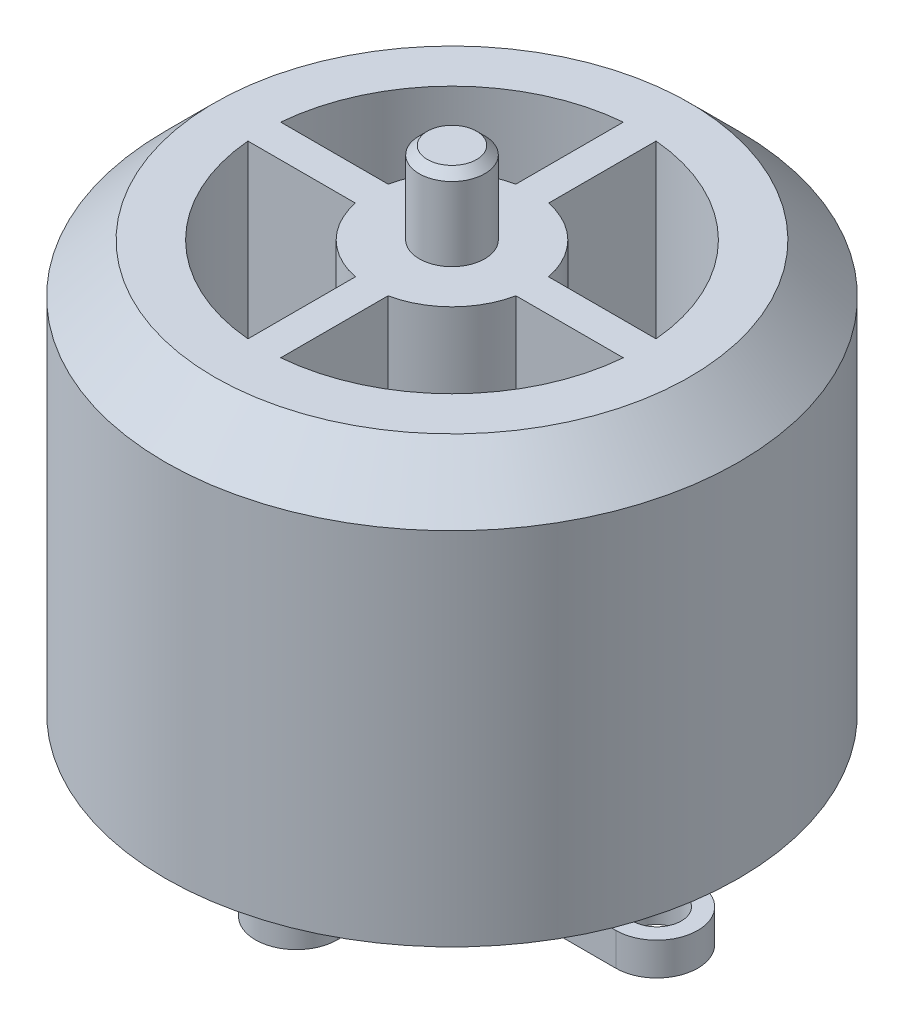
SolidWorks part; units mm, degrees
ref_plane "정면" through (0, 0, 0) normal (0, 0, 1) x (1, 0, 0)
ref_plane "윗면" through (0, 0, 0) normal (0, 1, 0) x (1, 0, 0)
ref_plane "우측면" through (0, 0, 0) normal (1, 0, 0) x (0, 0, -1)
sketch "스케치1" plane through (0, 0, 0) normal (0, 1, 0) x (1, 0, 0)
  line L0 (0, -9.5) -> (0, 9.5) construction
  line L1 (-12.5, 0) -> (12.5, 0) construction
  line L2 (0, -9.5) -> (0, 9.5) construction
  line L3 (-2.5, -9.5) -> (-2.5, 9.5)
  line L4 (2.5, -9.5) -> (2.5, 9.5)
  line L5 (-12.5, 0) -> (12.5, 0) construction
  line L6 (-12.5, 2.5) -> (12.5, 2.5)
  line L7 (-12.5, -2.5) -> (12.5, -2.5)
  circle A0 centre (0, 9.5) radius 1.5
  circle A1 centre (0, -9.5) radius 1.5
  circle A2 centre (-8, 0) radius 1.5
  circle A3 centre (8, 0) radius 1.5
  circle A4 centre (-12.5, 0) radius 1.5
  circle A5 centre (12.5, 0) radius 1.5
  arc A6 (-2.5, -9.5) -> (2.5, -9.5) centre (0, -9.5) ccw
  arc A7 (2.5, 9.5) -> (-2.5, 9.5) centre (0, 9.5) ccw
  arc A8 (-12.5, 2.5) -> (-12.5, -2.5) centre (-12.5, 0) ccw
  arc A9 (12.5, -2.5) -> (12.5, 2.5) centre (12.5, 0) ccw
  circle A10 centre (0, 0) radius 2
  point P4 (0, 0)
  point P8 (0, 0)
  point P17 (0, 0)
  point P23 (0, 0)
  dimension "D1" = 3
  dimension "D5" = 1
  dimension "D6" = 4
  dimension "D2" = 19
  dimension "D3" = 25
  dimension "D4" = 16
extrude "보스-돌출1" add sketch "스케치1" against normal blind 2 contours L6 A8 L7 L3 A4 A2 | A10 | L3 L7 L4 L6 A10 | L3 A6 L4 L7 A1 | L4 A7 L3 L6 A0 | L7 A9 L6 L4 A5 A3 region at (0, 0, 6.5308) region at (-7.5, 0, 2.3654) region at (-2.4293, 0, 0) region at (0, 0, -6.5308) region at (2.6346, 0, 0) region at (0, 0, 0)
extrude "보스-돌출2" add sketch "스케치1<3>" along normal blind 34 contours A10 region at (0, 0, 0)
sketch "스케치1<3>" plane through (0, 0, 0) normal (0, 1, 0) x (1, 0, 0) same geometry as "스케치1"
sketch "스케치2" plane through (0, 0, 0) normal (0, 1, 0) x (1, 0, 0)
  circle A0 centre (0, 0) radius 17.5
  dimension "D1" = 35
extrude "보스-돌출3" add sketch "스케치2" along normal blind 25 from offset 4
chamfer "모따기1" distance 3 angle 45 1 edges at (0, 29, 17.5)
sketch "스케치4" plane through (0, 29, 0) normal (0, 1, 0) x (1, 0, 0)
  line L0 (0, 12.5) -> (0, 4)
  line L1 (-4, 0) -> (-12.5, 0)
  line L2 (-1, 11.4564) -> (-1, 4.899)
  line L3 (-4.899, 1) -> (-11.4564, 1)
  line L4 (11.4564, 1) -> (4.899, 1)
  line L5 (1, 4.899) -> (1, 11.4564)
  line L6 (0, 4) -> (0, 12.5)
  line L7 (12.5, 0) -> (4, 0)
  line L8 (1, -11.4564) -> (1, -4.899)
  line L9 (4.899, -1) -> (11.4564, -1)
  line L10 (4, 0) -> (12.5, 0)
  line L11 (0, -12.5) -> (0, -4)
  line L12 (-11.4564, -1) -> (-4.899, -1)
  line L13 (-1, -4.899) -> (-1, -11.4564)
  line L14 (0, -4) -> (0, -12.5)
  line L15 (-12.5, 0) -> (-4, 0)
  arc A0 (0, 4) -> (-4, 0) centre (0, 0) ccw
  arc A1 (0, 12.5) -> (-12.5, 0) centre (0, 0) ccw
  circle A2 centre (0, 0) radius 14.5 construction
  arc A3 (-1, 4.899) -> (-4.899, 1) centre (0, 0) ccw
  arc A4 (-1, 11.4564) -> (-11.4564, 1) centre (0, 0) ccw
  arc A5 (4.899, 1) -> (1, 4.899) centre (0, 0) ccw
  arc A6 (11.4564, 1) -> (1, 11.4564) centre (0, 0) ccw
  arc A7 (12.5, 0) -> (0, 12.5) centre (0, 0) ccw
  arc A8 (4, 0) -> (0, 4) centre (0, 0) ccw
  arc A9 (1, -4.899) -> (4.899, -1) centre (0, 0) ccw
  arc A10 (1, -11.4564) -> (11.4564, -1) centre (0, 0) ccw
  arc A11 (0, -12.5) -> (12.5, 0) centre (0, 0) ccw
  arc A12 (0, -4) -> (4, 0) centre (0, 0) ccw
  arc A13 (-4.899, -1) -> (-1, -4.899) centre (0, 0) ccw
  arc A14 (-11.4564, -1) -> (-1, -11.4564) centre (0, 0) ccw
  arc A15 (-12.5, 0) -> (0, -12.5) centre (0, 0) ccw
  arc A16 (-4, 0) -> (0, -4) centre (0, 0) ccw
  point P41 (0, 0)
  dimension "D1" = 2
  dimension "D2" = 8
  dimension "D3" = 1
  dimension "D4" = 4
extrude "컷-돌출1" cut sketch "스케치4" against normal blind 25 contours L2 A4 L3 A3 | L12 A14 L13 A13 | L4 A6 L5 A5 | L8 A10 L9 A9 region at (-5.7363, 29, -5.7363) region at (5.7363, 29, -5.7363) region at (5.7363, 29, 5.7363) region at (-5.7363, 29, 5.7363)
chamfer "모따기2" distance 0.5 angle 45 1 edges at (0, 34, 2)
